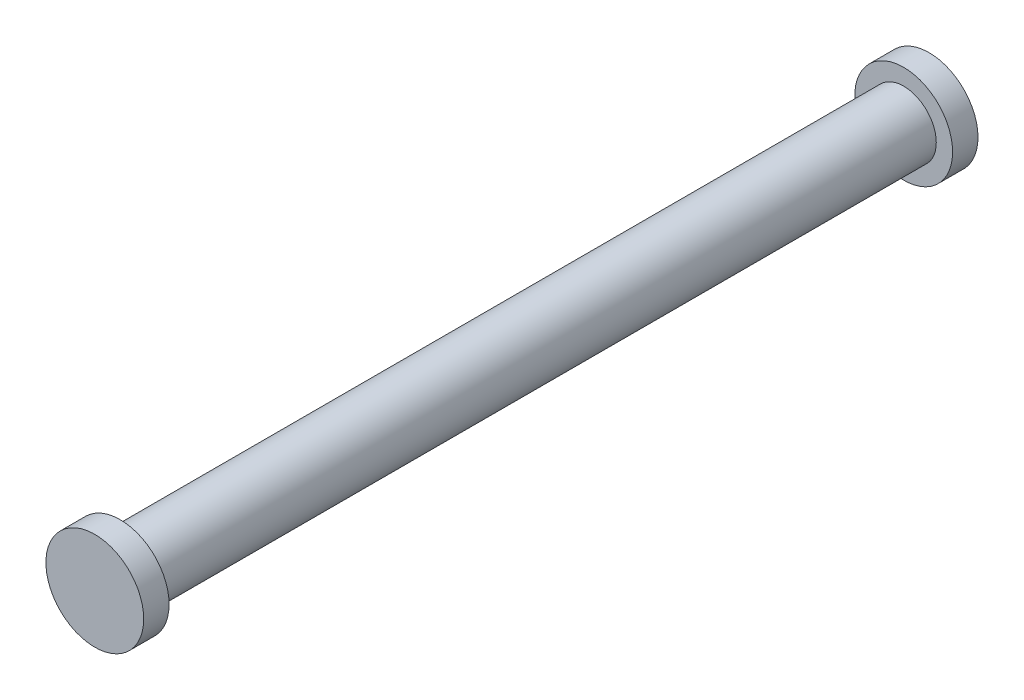
SolidWorks part; units mm, degrees
ref_plane "Front Plane" through (0, 0, 0) normal (0, 0, 1) x (1, 0, 0)
ref_plane "Top Plane" through (0, 0, 0) normal (0, 1, 0) x (1, 0, 0)
ref_plane "Right Plane" through (0, 0, 0) normal (1, 0, 0) x (0, 0, -1)
sketch "Sketch1" plane through (0, 0, 0) normal (0, 0, 1) x (1, 0, 0)
  circle A0 centre (0, 0) radius 5
  circle A1 centre (0, 0) radius 7.5
  dimension "D1" = 10
  dimension "D2" = 15
extrude "Boss-Extrude1" add sketch "Sketch1" along normal blind 128 contours A0 | A1 A0 region at (0, 0, 0) region at (-7.2879, 0, 0)
extrude "Cut-Extrude1" cut sketch "Sketch1<6>" along normal offset from surface (120.2 mm away) 3.9 from offset 3.9 contours A1 A0 region at (-7.2879, 0, 0) up to face at (7.5, 0, 128)
sketch "Sketch1<6>" plane through (0, 0, 0) normal (0, 0, 1) x (1, 0, 0) same geometry as "Sketch1"
